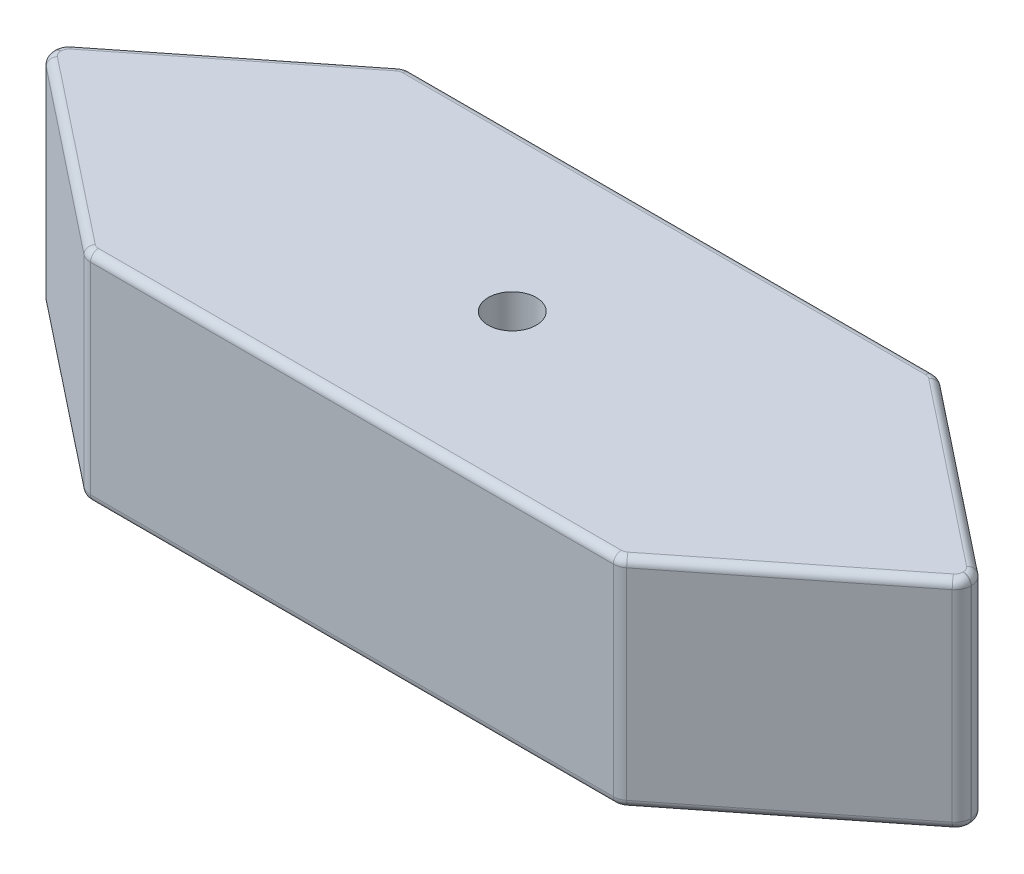
SolidWorks part; units mm, degrees
ref_plane "Front Plane" through (0, 0, 0) normal (0, 0, 1) x (1, 0, 0)
ref_plane "Top Plane" through (0, 0, 0) normal (0, 1, 0) x (1, 0, 0)
ref_plane "Right Plane" through (0, 0, 0) normal (1, 0, 0) x (0, 0, -1)
sketch "Sketch1" plane through (0, 0, 0) normal (0, 0, 1) x (1, 0, 0)
  line L1 (0, 238.8169) -> (182.0992, 238.8169)
  line L2 (0, 238.8169) -> (0, 195.7077)
  line L3 (0, 195.7077) -> (182.0992, 195.7077)
  line L4 (182.0992, 238.8169) -> (182.0992, 195.7077)
extrude "Boss-Extrude1" add sketch "Sketch1" along normal blind 31.75 and the other way blind 31.75
sketch "Sketch2" plane through (0, 238.8169, 0) normal (0, 1, 0) x (1, 0, 0)
  line L0 (1.2043, -2.5409) -> (37.2339, -31.0643)
  line L1 (0, 31.75) -> (0, -31.75) construction
  line L2 (182.0992, -31.75) -> (0, -31.75) construction
  line L3 (39.2046, -31.75) -> (142.8946, -31.75)
  line L4 (144.8653, -31.0643) -> (180.8949, -2.5409)
  line L5 (182.0992, 31.75) -> (182.0992, -31.75) construction
  line L6 (182.0992, -0.0515) -> (182.0992, 0.0515)
  line L7 (180.8949, 2.5409) -> (144.8653, 31.0643)
  line L8 (182.0992, 31.75) -> (0, 31.75) construction
  line L9 (142.8946, 31.75) -> (39.2046, 31.75)
  line L10 (37.2339, 31.0643) -> (1.2043, 2.5409)
  line L11 (0, 0.0515) -> (0, -0.0515)
  line L13 (-13.4791, 50.0479) -> (192.18, 50.0479)
  line L14 (-13.4791, 50.0479) -> (-13.4791, -49.0982)
  line L15 (-13.4791, -49.0982) -> (192.18, -49.0982)
  line L16 (192.18, 50.0479) -> (192.18, -49.0982)
  arc A0 (1.2043, 2.5409) -> (0, 0.0515) centre (3.175, 0.0515) ccw
  arc A1 (1.2043, -2.5409) -> (0, -0.0515) centre (3.175, -0.0515) cw
  arc A2 (37.2339, -31.0643) -> (39.2046, -31.75) centre (39.2046, -28.575) ccw
  arc A3 (142.8946, -31.75) -> (144.8653, -31.0643) centre (142.8946, -28.575) ccw
  arc A4 (180.8949, -2.5409) -> (182.0992, -0.0515) centre (178.9242, -0.0515) ccw
  arc A5 (182.0992, 0.0515) -> (180.8949, 2.5409) centre (178.9242, 0.0515) ccw
  arc A6 (144.8653, 31.0643) -> (142.8946, 31.75) centre (142.8946, 28.575) ccw
  arc A7 (39.2046, 31.75) -> (37.2339, 31.0643) centre (39.2046, 28.575) ccw
  point P24 (0, 1.5875)
  point P27 (0, -1.5875)
  point P30 (38.1, -31.75)
  point P33 (143.9992, -31.75)
  point P36 (182.0992, -1.5875)
  point P39 (182.0992, 1.5875)
  point P42 (143.9992, 31.75)
  point P45 (38.1, 31.75)
  dimension "D5" = 3.175
  dimension "D1" = 1.5875
  dimension "D2" = 1.5875
  dimension "D3" = 38.1
  dimension "D4" = 38.1
extrude "Cut-Extrude1" cut sketch "Sketch2" against normal through all
sketch "Sketch3" plane through (0, 195.7077, 0) normal (0, -1, 0) x (1, 0, 0)
  line L0 (39.2046, 31.75) -> (142.8946, 31.75) construction
  circle A0 centre (91.0496, -0.0515) radius 4.7625
  point P2 (91.0496, 31.75)
  dimension "D1" = 9.525
extrude "Cut-Extrude2" cut sketch "Sketch3" against normal through all
fillet "Fillet1" radius 1.5875 32 edges at (143.9379, 238.8169, 31.5737) (162.8801, 238.8169, 16.8026) (181.7823, 238.8169, 1.4342) (182.0992, 238.8169, 0) (181.7823, 238.8169, -1.4342) (162.8801, 238.8169, -16.8026) (143.9379, 238.8169, -31.5737) (91.0496, 238.8169, -31.75) (38.1613, 238.8169, -31.5737) (19.2191, 238.8169, -16.8026) (0.3169, 238.8169, -1.4342) (0, 238.8169, 0) (0.3169, 238.8169, 1.4342) (19.2191, 238.8169, 16.8026) (38.1613, 238.8169, 31.5737) (38.1613, 195.7077, 31.5737) (19.2191, 195.7077, 16.8026) (0.3169, 195.7077, 1.4342) (0, 195.7077, 0) (0.3169, 195.7077, -1.4342) (19.2191, 195.7077, -16.8026) (38.1613, 195.7077, -31.5737) (91.0496, 195.7077, -31.75) (143.9379, 195.7077, -31.5737) (162.8801, 195.7077, -16.8026) (181.7823, 195.7077, -1.4342) (182.0992, 195.7077, 0) (181.7823, 195.7077, 1.4342) (162.8801, 195.7077, 16.8026) (143.9379, 195.7077, 31.5737) (91.0496, 238.8169, 31.75) (91.0496, 195.7077, 31.75)
